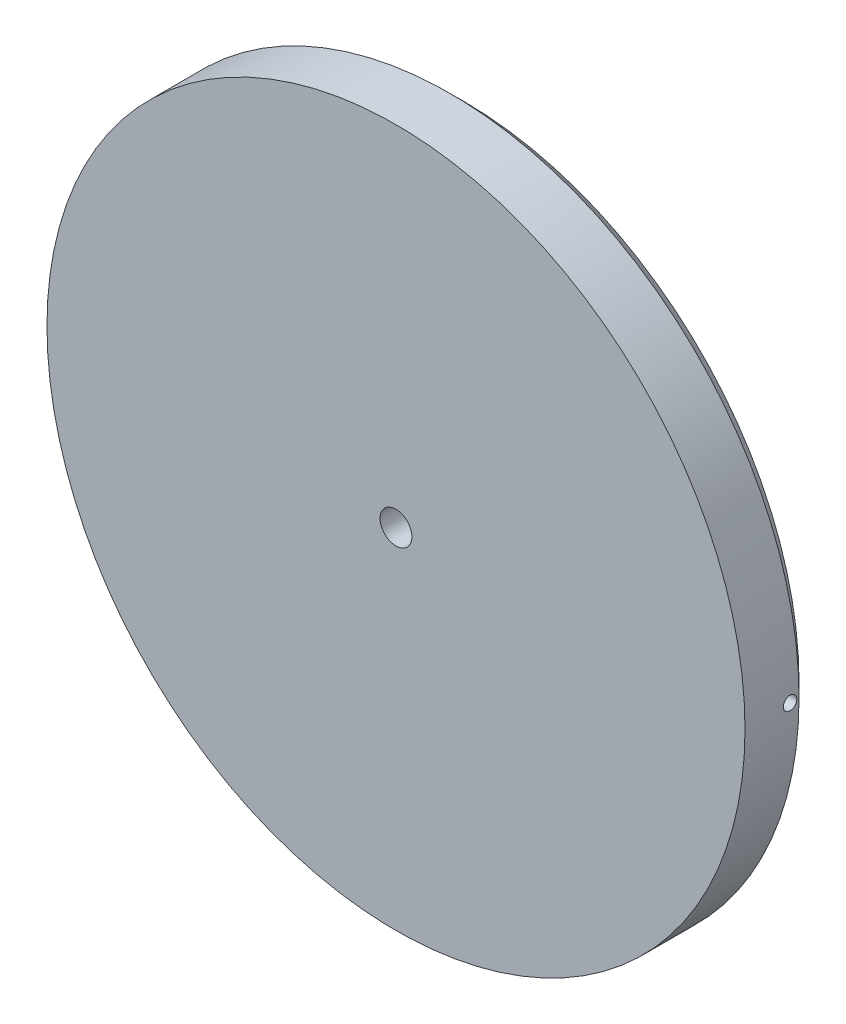
SolidWorks part; units mm, degrees
ref_plane "Front Plane" through (0, 0, 0) normal (0, 0, 1) x (1, 0, 0)
ref_plane "Top Plane" through (0, 0, 0) normal (0, 1, 0) x (1, 0, 0)
ref_plane "Right Plane" through (0, 0, 0) normal (1, 0, 0) x (0, 0, -1)
ref_axis "Z" through (0, 0, 543.0939) along (0, 0, -1)
ref_axis "X" through (17.0818, 0, 0) along (-1, 0, 0)
ref_axis "Y" through (0, 20.242, 0) along (0, -1, 0)
sketch "Sketch1" plane through (0, 0, 0) normal (0, 0, 1) x (1, 0, 0)
  circle A0 centre (0, 0) radius 77.5
  circle A1 centre (0, 0) radius 3.535
  dimension "D1" = 155
  dimension "D2" = 7.07
extrude "Boss-Extrude1" add sketch "Sketch1" against normal blind 5 and the other way blind 10
sketch "Sketch2" plane through (0, 0, 0) normal (0, 1, 0) x (1, 0, 0)
  line L0 (-16.3173, 0) -> (16.3173, 0) construction
  line L1 (0, -20.5521) -> (0, 20.5521) construction
  circle A0 centre (0, 0) radius 1.5
  dimension "D1" = 3
extrude "Cut-Extrude1" cut sketch "Sketch2" against normal through all
sketch "Sketch3" plane through (0, 0, 0) normal (1, 0, 0) x (0, 0, -1)
  circle A0 centre (0, 0) radius 1.5
  dimension "D1" = 3
extrude "Cut-Extrude2" cut sketch "Sketch3" along normal through all
chamfer "Chamfer1" distance 3 angle 45 1 edges at (77.5, 0, -5)
sketch "Sketch4" plane through (0, 0, 0) normal (0, 0, 1) x (1, 0, 0)
  circle A0 centre (0, 0) radius 3.535
  circle A2 centre (0, 0) radius 3.535 construction
  circle A3 centre (0, 0) radius 71.5
  dimension "D1" = 143
extrude "Boss-Extrude2" add sketch "Sketch4" along normal up to surface and the other way up to surface up to face at (77.5, 0, 10) other way up to face at (74.5, 0, -5)
sketch "Sketch5" plane through (0, 0, 0) normal (0, 0, 1) x (1, 0, 0)
  line L0 (0, 0) -> (0, -94.5) construction
  dimension "D1" = 94.5
equation "\"EyeDiameter\" = 155"
equation "\"BasePlaneDistance\" = \"EyeDiameter\"/2+\"L2Thickness\"+\"EyeClearance\""
equation "\"EyeClearance\" = 2"
equation "\"EyeOD\"= \"EyeDiameter\""
equation "\"D1@Sketch1\"=\"EyeOD\""
equation "\"D2@Sketch1\"= 7.07"
equation "\"pinHoleDiameter\"= 3"
equation "\"D1@Sketch2\"=\"pinHoleDiameter\""
equation "\"D1@Sketch3\"=\"pinHoleDiameter\""
equation "\"D1@Sketch4\"=\"EyeDiameter\"-12"
equation "\"D1@Sketch5\"=\"BasePlaneDistance\""
